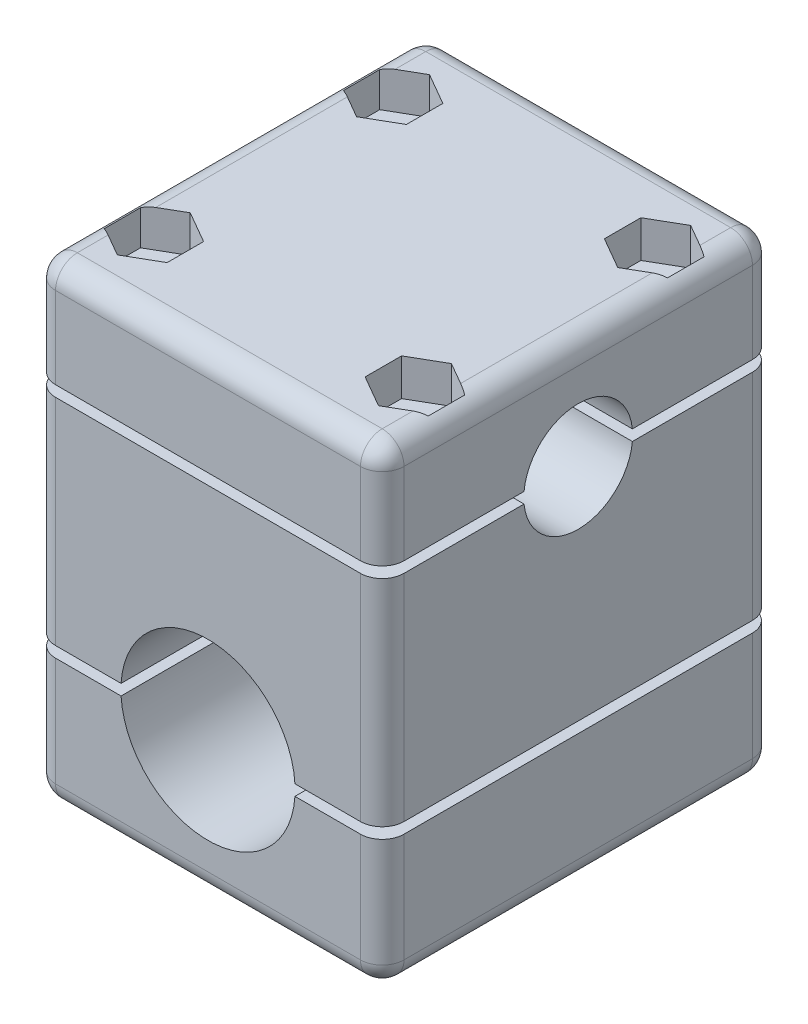
SolidWorks part; units mm, degrees
ref_plane "Front" through (0, 0, 0) normal (0, 0, 1) x (1, 0, 0)
ref_plane "Top" through (0, 0, 0) normal (0, 1, 0) x (1, 0, 0)
ref_plane "Right" through (0, 0, 0) normal (1, 0, 0) x (0, 0, -1)
sketch "Sketch1" plane through (0, 0, 0) normal (1, 0, 0) x (0, 0, -1)
  line L0 (-18, 0) -> (-5, 0) construction
  line L1 (5, 0) -> (18, 0) construction
  line L2 (-18, -10) -> (-18, 10)
  line L3 (-18, 10) -> (18, 10)
  line L4 (18, 10) -> (18, -10)
  line L10 (-18, 0.5) -> (-4.9749, 0.5)
  line L11 (4.9749, 0.5) -> (18, 0.5)
  line L12 (-18, -0.5) -> (-4.9749, -0.5)
  line L13 (4.9749, -0.5) -> (18, -0.5)
  line L14 (-18, -10) -> (18, -10) construction
  line L15 (-18, -10) -> (-18, -20.2453)
  line L16 (-18, -20.2453) -> (18, -20.2453)
  line L17 (18, -20.2453) -> (18, -10)
  circle A0 centre (0, 0) radius 5
  point P18 (0, 10)
  dimension "D1" = 5
  dimension "D2" = 0.5
  dimension "D3" = 36
  dimension "D4" = 10
extrude "Boss-Extrude1" add sketch "Sketch1" along normal blind 32 contours L10 A0 L11 L4 L3 L2 | L13 A0 L12 L2 L15 L16 L17 L4 region at (0, -10.7768, 0) region at (0, 5.5681, 0)
sketch "Sketch2" plane through (0, 0, 18) normal (0, 0, 1) x (1, 0, 0)
  line L0 (32, -20.2453) -> (0, -20.2453) construction
  arc A1 (8.0156, -20.2453) -> (23.9844, -20.2453) centre (16, -20.7453) cw
  point P6 (16, -20.2453)
  line M13 (0, -20.2453) -> (32, -20.2453)
  dimension "D2" = 8
  dimension "D1" = 0.5
extrude "Cut-Extrude3" cut sketch "Sketch2" against normal through all contours A1 M13 region at (16, -17.0782, 18)
sketch "Sketch3" plane through (0, 0, 18) normal (0, 0, 1) x (1, 0, 0)
  line L0 (32, -20.2453) -> (23.9844, -20.2453) construction
  line L1 (8.0156, -20.2453) -> (0, -20.2453) construction
  line L2 (32, -20.2453) -> (23.9844, -20.2453) construction
  line L3 (8.0156, -20.2453) -> (0, -20.2453) construction
  line L4 (16, -20.7453) -> (36.5538, -20.7453) construction
  line L5 (32, -21.2453) -> (23.9844, -21.2453)
  line L6 (8.0156, -21.2453) -> (0, -21.2453)
  line L7 (0, -21.2453) -> (0, -33.2453)
  line L8 (0, -33.2453) -> (32, -33.2453)
  line L9 (32, -33.2453) -> (32, -21.2453)
  arc A0 (23.9844, -20.2453) -> (8.0156, -20.2453) centre (16, -20.7453) ccw construction
  arc A1 (23.9844, -20.2453) -> (8.0156, -20.2453) centre (16, -20.7453) ccw construction
  arc A2 (23.9844, -21.2453) -> (8.0156, -21.2453) centre (16, -20.7453) cw
  dimension "D1" = 12
extrude "Boss-Extrude2" add sketch "Sketch3" against normal up to surface (36 mm away) separate body contours L7 L8 L9 L5 A2 L6 up to face at (16, -12.4135, -18)
sketch "Sketch5" plane through (0, -21.2453, 0) normal (0, 1, 0) x (1, 0, 0)
  line L0 (0, 18) -> (8.0156, 18) construction
  line L2 (0, 0) -> (32, 0) construction
  line L3 (32, -18) -> (32, 18) construction
  line L4 (16, 18) -> (16, -18) construction
  line L5 (32, 18) -> (0, 18) construction
  line L6 (32, -18) -> (0, -18) construction
  circle A1 centre (4.0078, 10.9875) radius 1.475
  circle A2 centre (27.9922, 10.9875) radius 1.475
  circle A3 centre (27.9922, -10.9875) radius 1.475
  circle A4 centre (4.0078, -10.9875) radius 1.475
  point P4 (4.0078, 18)
  dimension "D1" = 2.95
extrude "Cut-Extrude4" cut sketch "Sketch5" against normal through all both and the other way through all
ref_plane "Plane1" through (0, 10, 0) normal (0, 1, 0) x (1, 0, 0)
sketch "Sketch7" plane through (0, 10, 0) normal (0, 1, 0) x (1, 0, 0)
  line L0 (0, 0) -> (32, 0) construction
  line L1 (6.9078, 9.3132) -> (6.9078, 12.6618)
  line L2 (6.9078, 12.6618) -> (4.0078, 14.3361)
  line L3 (4.0078, 14.3361) -> (1.1078, 12.6618)
  line L4 (1.1078, 12.6618) -> (1.1078, 9.3132)
  line L5 (1.1078, 9.3132) -> (4.0078, 7.6388)
  line L6 (4.0078, 7.6388) -> (6.9078, 9.3132)
  line L7 (16, 18) -> (16, -18) construction
  line L8 (0, 0) -> (32, 0) construction
  line L9 (16, 18) -> (16, -18) construction
  line L10 (27.9922, 7.6388) -> (25.0922, 9.3132)
  line L11 (30.8922, 9.3132) -> (27.9922, 7.6388)
  line L12 (30.8922, 12.6618) -> (30.8922, 9.3132)
  line L13 (27.9922, 14.3361) -> (30.8922, 12.6618)
  line L14 (25.0922, 12.6618) -> (27.9922, 14.3361)
  line L15 (25.0922, 9.3132) -> (25.0922, 12.6618)
  line L16 (25.0922, -9.3132) -> (25.0922, -12.6618)
  line L17 (25.0922, -12.6618) -> (27.9922, -14.3361)
  line L18 (27.9922, -14.3361) -> (30.8922, -12.6618)
  line L19 (30.8922, -12.6618) -> (30.8922, -9.3132)
  line L20 (30.8922, -9.3132) -> (27.9922, -7.6388)
  line L21 (27.9922, -7.6388) -> (25.0922, -9.3132)
  line L22 (4.0078, -7.6388) -> (6.9078, -9.3132)
  line L23 (1.1078, -9.3132) -> (4.0078, -7.6388)
  line L24 (1.1078, -12.6618) -> (1.1078, -9.3132)
  line L25 (4.0078, -14.3361) -> (1.1078, -12.6618)
  line L26 (6.9078, -12.6618) -> (4.0078, -14.3361)
  line L27 (6.9078, -9.3132) -> (6.9078, -12.6618)
  circle A0 centre (4.0078, 10.9875) radius 1.475 construction
  circle A1 centre (4.0078, 10.9875) radius 1.475
  circle A2 centre (4.0078, 10.9875) radius 2.9 construction
  circle A3 centre (27.9922, 10.9875) radius 2.9 construction
  circle A4 centre (27.9922, 10.9875) radius 1.475
  circle A5 centre (27.9922, -10.9875) radius 2.9 construction
  circle A6 centre (4.0078, -10.9875) radius 2.9 construction
  circle A7 centre (27.9922, -10.9875) radius 1.475
  circle A8 centre (4.0078, -10.9875) radius 1.475
  dimension "D1" = 5.8
extrude "Cut-Extrude5" cut sketch "Sketch7" against normal blind 3.4
ref_plane "Plane2" through (0, -33.2453, 0) normal (0, -1, 0) x (-1, 0, 0)
sketch "Sketch8" plane through (0, -33.2453, 0) normal (0, -1, 0) x (-1, 0, 0)
  line L0 (-16, 18) -> (-16, -18) construction
  line L1 (0, 0) -> (-32, 0) construction
  line L2 (-16, 18) -> (-16, -18) construction
  line L3 (0, 0) -> (-32, 0) construction
  circle A2 centre (-27.9922, 10.9875) radius 2.75
  circle A3 centre (-4.0078, 10.9875) radius 2.75
  circle A4 centre (-4.0078, -10.9875) radius 2.75
  circle A5 centre (-27.9922, -10.9875) radius 2.75
  dimension "D1" = 5.5
extrude "Cut-Extrude6" cut sketch "Sketch8" against normal blind 3.5
fillet "Fillet1" radius 2 8 edges at (16, 10, 18) (0, 10, 0) (32, 10, 0) (16, 10, -18) (0, 5.25, -18) (0, 5.25, 18) (32, 5.25, -18) (32, 5.25, 18)
fillet "Fillet2" radius 2 4 edges at (32, -10.3726, 18) (0, -10.3726, 18) (0, -10.3726, -18) (32, -10.3726, -18)
fillet "Fillet3" radius 2 8 edges at (16, -33.2453, 18) (0, -33.2453, 0) (16, -33.2453, -18) (32, -33.2453, 0) (32, -27.2453, -18) (32, -27.2453, 18) (0, -27.2453, -18) (0, -27.2453, 18)
